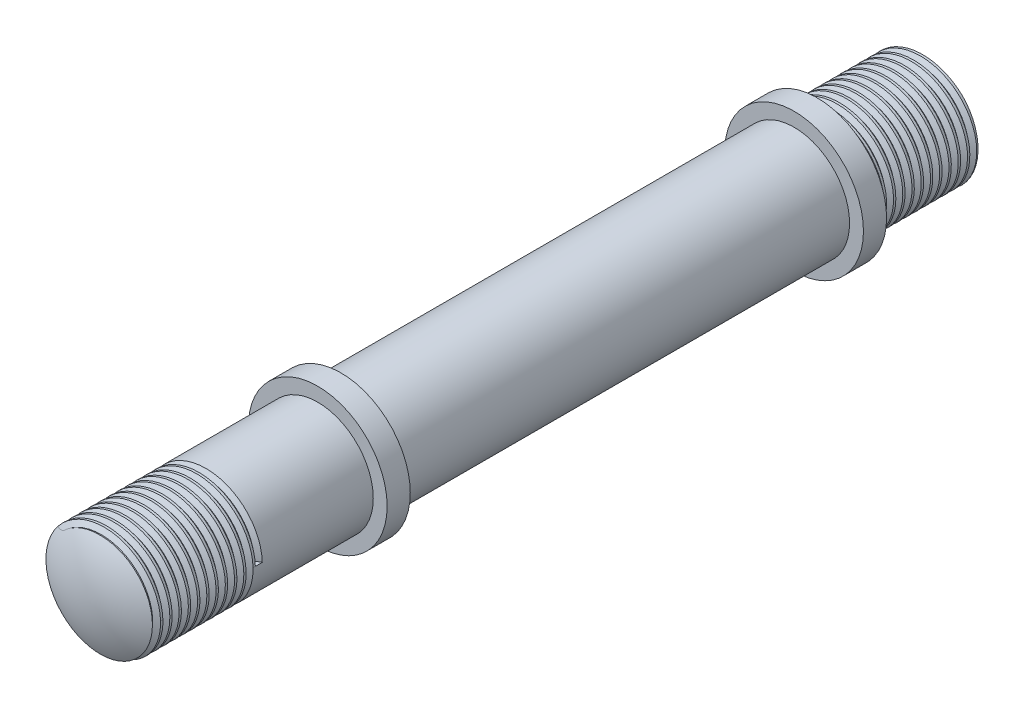
SolidWorks part; units mm, degrees
ref_plane "Front Plane" through (0, 0, 0) normal (0, 0, 1) x (1, 0, 0)
ref_plane "Top Plane" through (0, 0, 0) normal (0, 1, 0) x (1, 0, 0)
ref_plane "Right Plane" through (0, 0, 0) normal (1, 0, 0) x (0, 0, -1)
sketch "Sketch1" plane through (0, 0, 0) normal (1, 0, 0) x (0, 0, -1)
  line L0 (0, 0) -> (0, -16296.2134) construction
  line L1 (0, 0) -> (16296.2134, 0) construction
  line L2 (0, 0) -> (184, 0)
  line L3 (184, 0) -> (184, -12)
  line L4 (184, -12) -> (158, -12)
  line L5 (158, -12) -> (158, -15)
  line L6 (158, -15) -> (153, -15)
  line L7 (153, -15) -> (153, -12)
  line L8 (153, -12) -> (55, -12)
  line L9 (55, -12) -> (55, -15)
  line L10 (55, -15) -> (50, -15)
  line L11 (50, -15) -> (50, -12)
  line L12 (50, -12) -> (0, -12)
  line L13 (0, -12) -> (0, 0)
  arc A0 (3.2154, -12) -> (3.2154, 12) centre (24, 0) cw
  arc A1 (180.7846, -12) -> (180.7846, 12) centre (160, 0) ccw
  dimension "D8" = 24
  dimension "D10" = 24
  dimension "D1" = 24
  dimension "D2" = 98
  dimension "D3" = 5
  dimension "D4" = 5
  dimension "D5" = 24
  dimension "D6" = 30
  dimension "D7" = 50
  dimension "D9" = 26
revolve "Revolve5" add sketch "Sketch1" angle 360 about L1 region at (0, -6.0673, -92.1627)
thread "Thread1" pitch 2 method cut profile "Thread Profile1" start angle 0, offset 24, length 26, pitch 2, diameter 24
ref_plane "Plane1" through (12, 0, -26) normal (0, 1, 0) x (-1, 0, 0)
sketch "Thread Profile1" plane through (12, 0, -26) normal (0, 1, 0) x (-1, 0, 0)
  line L0 (0, 0) -> (0, 2) construction
  line L1 (0, 0) -> (1.0825, 0.625)
  line L2 (1.0825, 0.625) -> (1.0825, 0.875)
  line L3 (1.0825, 0.875) -> (0, 1.5)
  line L4 (1.0825, 0.75) -> (0, 0.75) construction
  line L11 (0, 0) -> (0, 1.5)
  point P2 (0, 0)
  dimension "Pitch" = 2
  dimension "Profile_Angle" = 60
  dimension "Profile_Land" = 0.25
  dimension "Profile_Height" = 1.0825
thread "Thread2" pitch 2 method cut profile "Thread Profile2" start angle 0, offset 0, length 26, pitch 2, diameter 24
ref_plane "Plane2" through (-12, 0, -158) normal (0, 1, 0) x (1, 0, 0)
sketch "Thread Profile2" plane through (-12, 0, -158) normal (0, 1, 0) x (1, 0, 0)
  line L0 (0, 0) -> (0, 2) construction
  line L1 (0, 0) -> (1.0825, 0.625)
  line L2 (1.0825, 0.625) -> (1.0825, 0.875)
  line L3 (1.0825, 0.875) -> (0, 1.5)
  line L4 (1.0825, 0.75) -> (0, 0.75) construction
  line L11 (0, 0) -> (0, 1.5)
  point P2 (0, 0)
  dimension "Pitch" = 2
  dimension "Profile_Angle" = 60
  dimension "Profile_Land" = 0.25
  dimension "Profile_Height" = 1.0825
